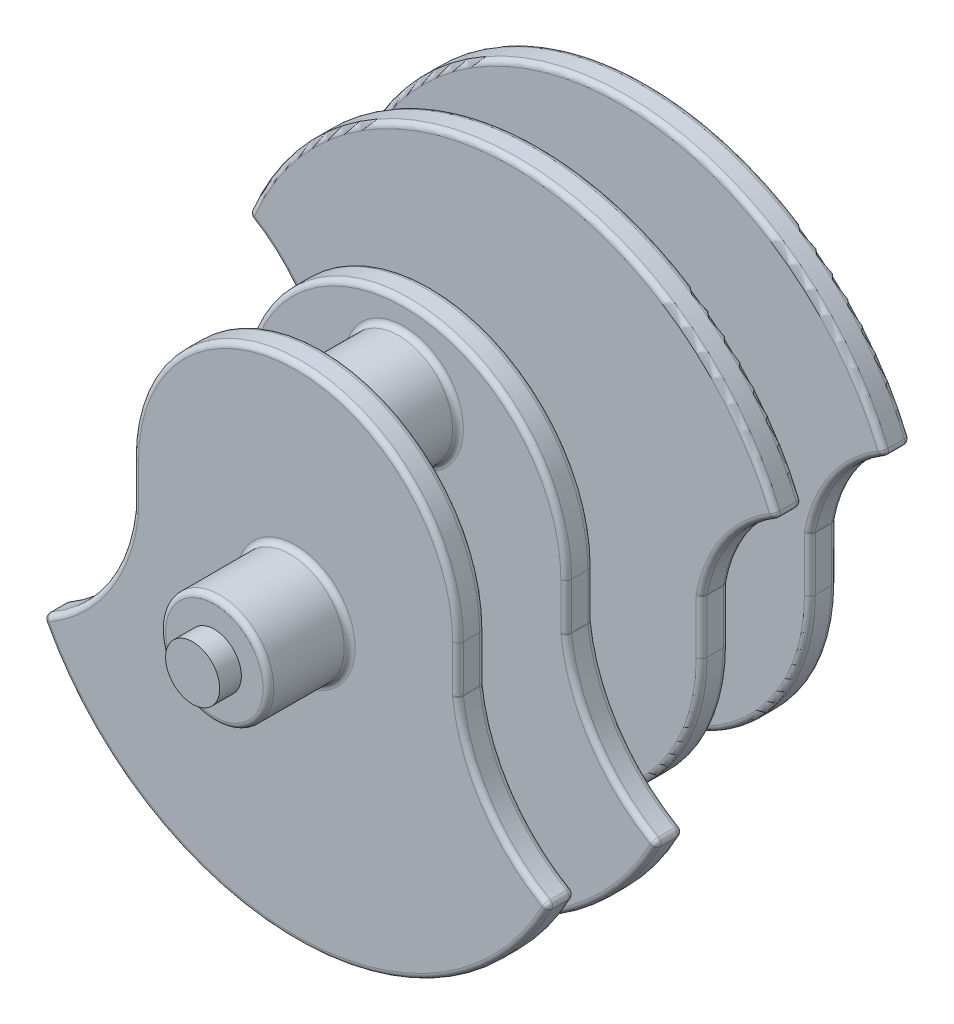
SolidWorks part; units mm, degrees
material "AISI 4340 Steel, normalized"
ref_plane "Front Plane" through (0, 0, 0) normal (0, 0, 1) x (1, 0, 0)
ref_plane "Top Plane" through (0, 0, 0) normal (0, 1, 0) x (1, 0, 0)
ref_plane "Right Plane" through (0, 0, 0) normal (1, 0, 0) x (0, 0, -1)
sketch "Sketch1" plane through (0, 0, 0) normal (0, 0, 1) x (1, 0, 0)
  circle A0 centre (0, 0) radius 20
  dimension "D1" = 20
extrude "Boss-Extrude1" add sketch "Sketch1" along normal blind 30
sketch "Sketch2" plane through (0, 0, 30) normal (0, 0, 1) x (1, 0, 0)
  circle A0 centre (0, 0) radius 10
  dimension "D1" = 10
extrude "Boss-Extrude2" add sketch "Sketch2" along normal blind 8
sketch "Sketch8" plane through (0, 0, 0) normal (0, 0, -1) x (-1, 0, 0)
  line L0 (-60, 20) -> (-60, 2.7836)
  line L1 (60, 20) -> (60, 2.7836)
  arc A0 (60, 20) -> (-60, 20) centre (0, 20) ccw
  arc A5 (-93.6849, -47.4146) -> (93.6849, -47.4146) centre (0, 0) ccw
  arc A6 (-60, 2.7836) -> (-93.6849, -47.4146) centre (-125, 10) cw
  arc A7 (60, 2.7836) -> (93.6849, -47.4146) centre (125, 10) ccw
  dimension "D1" = 60
  dimension "D2" = 105
  dimension "D3" = 20
  dimension "D5" = 10
  dimension "D6" = 125
extrude "Boss-Extrude5" add sketch "Sketch8" along normal blind 10
sketch "Sketch9" plane through (0, 0, -10) normal (0, 0, -1) x (-1, 0, 0)
  circle A0 centre (0, 50) radius 20
  dimension "D2" = 20
  dimension "D1" = 50
extrude "Boss-Extrude6" add sketch "Sketch9" along normal blind 30
ref_plane "Plane4" through (0, 0, -80) normal (0, 0, -1) x (-1, 0, 0)
sketch "Sketch10" plane through (0, 0, -40) normal (0, 0, -1) x (-1, 0, 0)
  line L0 (-70, -20) -> (-70, 0)
  line L1 (70, -20) -> (70, 0)
  arc A0 (-70, -20) -> (70, -20) centre (0, -20) ccw
  arc A1 (-70, 0) -> (-97.598, 38.7251) centre (-125, -10) ccw
  arc A2 (70, 0) -> (97.598, 38.7251) centre (125, -10) cw
  arc A3 (-97.598, 38.7251) -> (97.598, 38.7251) centre (0, 0) cw
  dimension "D1" = 70
  dimension "D3" = 105
  dimension "D2" = 20
  dimension "D4" = 125
  dimension "D5" = 10
extrude "Boss-Extrude7" add sketch "Sketch10" along normal blind 10 from surface starting at plane "Plane4"
ref_plane "Plane3" through (0, 0, -120) normal (0, 0, -1) x (-1, 0, 0)
sketch "Sketch12" plane through (0, 0, -120) normal (0, 0, -1) x (-1, 0, 0)
  line L2 (70, -20) -> (70, 0)
  line L3 (70, -20) -> (70, 0)
  line L4 (-70, 0) -> (-70, -20)
  line L5 (-70, 0) -> (-70, -20)
  arc A12 (-70, -20) -> (70, -20) centre (0, -20) ccw
  arc A13 (97.598, 38.7251) -> (70, 0) centre (125, -10) ccw
  arc A14 (97.598, 38.7251) -> (-97.598, 38.7251) centre (0, 0) ccw
  arc A15 (-70, 0) -> (-97.598, 38.7251) centre (-125, -10) ccw
  arc A16 (-70, -20) -> (70, -20) centre (0, -20) ccw
  arc A17 (97.598, 38.7251) -> (70, 0) centre (125, -10) ccw
  arc A18 (97.598, 38.7251) -> (-97.598, 38.7251) centre (0, 0) ccw
  arc A19 (-70, 0) -> (-97.598, 38.7251) centre (-125, -10) ccw
  dimension "D1" = 0
extrude "Boss-Extrude8" add sketch "Sketch12" along normal blind 10
sketch "Sketch14" plane through (0, 0, -90) normal (0, 0, -1) x (-1, 0, 0)
  circle A0 centre (0, -50) radius 20
  dimension "D2" = 20
  dimension "D1" = 50
extrude "Boss-Extrude9" add sketch "Sketch14" along normal up to next
sketch "Sketch15" plane through (0, 0, -130) normal (0, 0, -1) x (-1, 0, 0)
  circle A1 centre (0, 0) radius 20
  circle A2 centre (0, 0) radius 20
  dimension "D1" = 0
extrude "Boss-Extrude10" add sketch "Sketch15" along normal blind 30
sketch "Sketch16" plane through (0, 0, -160) normal (0, 0, -1) x (-1, 0, 0)
  circle A1 centre (0, 0) radius 10
  circle A2 centre (0, 0) radius 10
  dimension "D1" = 0
extrude "Boss-Extrude11" add sketch "Sketch16" along normal blind 8
sketch "Sketch18" plane through (0, 0, -40) normal (0, 0, -1) x (-1, 0, 0)
  line L2 (-60, 20) -> (-60, 2.7836)
  line L3 (-60, 20) -> (-60, 2.7836)
  line L4 (60, 2.7836) -> (60, 20)
  line L5 (60, 2.7836) -> (60, 20)
  arc A4 (60, 20) -> (-60, 20) centre (0, 20) ccw
  arc A5 (-93.6849, -47.4146) -> (-60, 2.7836) centre (-125, 10) ccw
  arc A6 (-93.6849, -47.4146) -> (93.6849, -47.4146) centre (0, 0) ccw
  arc A7 (60, 2.7836) -> (93.6849, -47.4146) centre (125, 10) ccw
  arc A8 (60, 20) -> (-60, 20) centre (0, 20) ccw
  arc A9 (-93.6849, -47.4146) -> (-60, 2.7836) centre (-125, 10) ccw
  arc A10 (-93.6849, -47.4146) -> (93.6849, -47.4146) centre (0, 0) ccw
  arc A11 (60, 2.7836) -> (93.6849, -47.4146) centre (125, 10) ccw
  dimension "D1" = 0
extrude "Boss-Extrude12" add sketch "Sketch18" along normal blind 10
sketch "Sketch19" plane through (0, 0, -50) normal (0, 0, -1) x (-1, 0, 0)
  circle A1 centre (0, 0) radius 20
  circle A2 centre (0, 0) radius 20
  dimension "D1" = 0
extrude "Boss-Extrude13" add sketch "Sketch19" along normal blind 30
fillet "Fillet1" radius 2 32 edges at (0, -105, -40) (-70.6942, -26.4412, -40) (-60, 11.3918, -40) (60, 11.3918, -40) (70.6942, -26.4412, -40) (0, -105, -50) (-70.6942, -26.4412, -50) (-60, 11.3918, -50) (0, 80, -50) (60, 11.3918, -50) (70.6942, -26.4412, -50) (93.6849, -47.4146, -45) (60, 2.7836, -45) (-60, 2.7836, -45) (-93.6849, -47.4146, -45) (0, 80, -40) (60, 11.3918, 0) (70.6942, -26.4412, 0) (0, -105, 0) (-70.6942, -26.4412, 0) (-60, 11.3918, 0) (0, 80, -10) (60, 11.3918, -10) (70.6942, -26.4412, -10) (0, -105, -10) (-70.6942, -26.4412, -10) (-60, 11.3918, -10) (-60, 2.7836, -5) (-93.6849, -47.4146, -5) (93.6849, -47.4146, -5) (60, 2.7836, -5) (0, 80, 0)
fillet "Fillet2" radius 2 16 edges at (0, 105, -120) (79.4761, 22.4433, -120) (70, -10, -120) (0, -90, -120) (-70, -10, -120) (-79.4761, 22.4433, -120) (79.4761, 22.4433, -130) (70, -10, -130) (0, -90, -130) (-70, -10, -130) (-79.4761, 22.4433, -130) (-97.598, 38.7251, -125) (-70, 0, -125) (70, 0, -125) (97.598, 38.7251, -125) (0, 105, -130)
fillet "Fillet3" radius 2 16 edges at (70, -10, -80) (79.4761, 22.4433, -80) (0, 105, -80) (-79.4761, 22.4433, -80) (-70, -10, -80) (0, -90, -80) (70, -10, -90) (79.4761, 22.4433, -90) (-79.4761, 22.4433, -90) (-70, -10, -90) (0, -90, -90) (70, 0, -85) (97.598, 38.7251, -85) (-97.598, 38.7251, -85) (-70, 0, -85) (0, 105, -90)
fillet "Fillet5" radius 2 2 edges at (20, 0, 30) (20, 0, 0)
fillet "Fillet6" radius 2 2 edges at (-20, 0, -130) (-20, 0, -160)
fillet "Fillet7" radius 2 2 edges at (-20, 50, -40) (-20, 50, -10)
fillet "Fillet8" radius 2 2 edges at (-20, 0, -50) (-20, 0, -80)
fillet "Fillet9" radius 2 2 edges at (-20, -50, -90) (-20, -50, -120)
equation "\"Crank Radius\"= 50mm"
equation "\"D1@Sketch9\"=\"Crank Radius\""
equation "\"D1@Sketch14\"=\"Crank Radius\""
